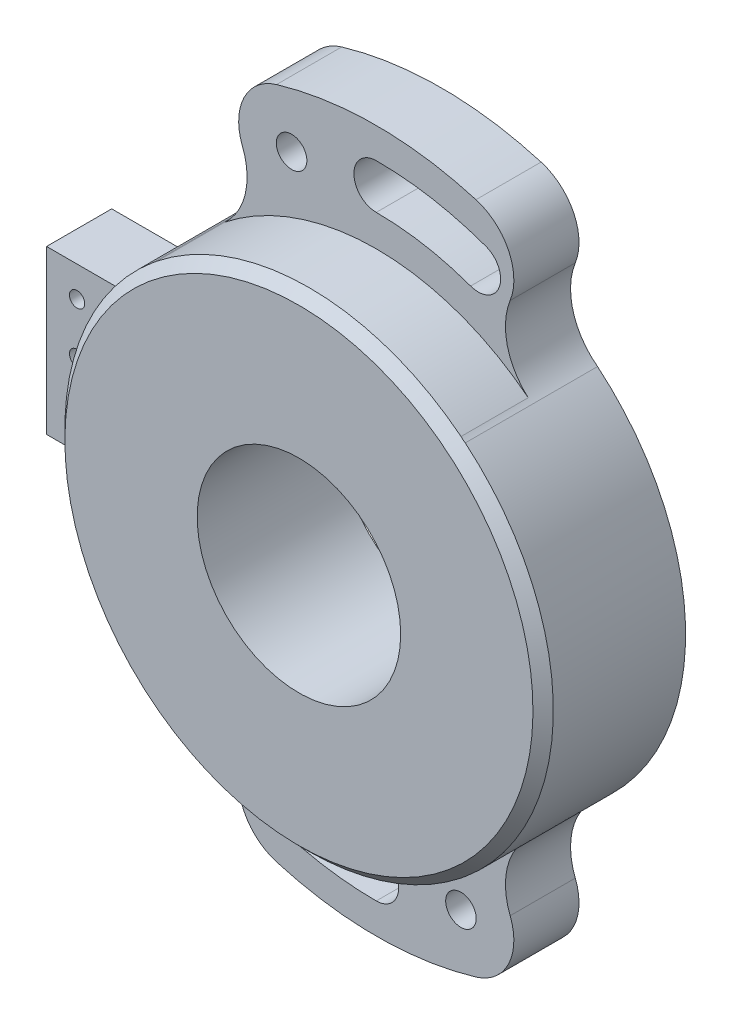
SolidWorks part; units mm, degrees
note: The reader was unsure of these and kept them because the rebuilt part matched: shared geometry of "Sketch1<3>".
material "PET"
ref_plane "Front Plane" through (0, 0, 0) normal (0, 0, 1) x (1, 0, 0)
ref_plane "Top Plane" through (0, 0, 0) normal (0, 1, 0) x (1, 0, 0)
ref_plane "Right Plane" through (0, 0, 0) normal (1, 0, 0) x (0, 0, -1)
sketch "Sketch1" plane through (0, 0, 0) normal (0, 0, 1) x (1, 0, 0)
  line L0 (5.8998, 16.2097) -> (-5.8998, -16.2097) construction
  line L1 (2.4007, 17.0821) -> (-2.4007, -17.0821) construction
  line L2 (-4.8993, 16.5396) -> (4.8993, -16.5396) construction
  line L3 (0, 17.25) -> (0, -17.25) construction
  line L4 (-17.25, 0) -> (17.25, 0) construction
  line L5 (0, -17.25) -> (0, 17.25) construction
  line L6 (-16.2, 4) -> (-16.2, -4)
  line L7 (-16.2, 4) -> (-11.3137, 4)
  line L8 (-16.2, -4) -> (-11.3137, -4)
  line L9 (-14.7, 4) -> (-14.7, -4) construction
  circle A0 centre (0, 0) radius 17.25 construction
  circle A1 centre (0, 0) radius 14.65 construction
  circle A2 centre (0, 0) radius 12
  circle A3 centre (-4.1608, 14.0467) radius 0.75
  arc A4 (0, 15.75) -> (5.3868, 14.8002) centre (0, 0) cw
  arc A5 (0, 13.55) -> (4.6344, 12.7328) centre (0, 0) cw
  arc A6 (5.3868, 14.8002) -> (4.6344, 12.7328) centre (5.0106, 13.7665) cw
  arc A7 (0, 13.55) -> (0, 15.75) centre (0, 14.65) cw
  arc A8 (-4.8993, 16.5396) -> (5.8998, 16.2097) centre (0, 0) cw
  arc A9 (-6.5784, 13.09) -> (-4.8993, 16.5396) centre (-4.1608, 14.0467) cw
  arc A10 (-6.5784, 13.09) -> (-7.6724, 9.2268) centre (-9.6516, 11.8738) cw
  arc A11 (6.5784, 13.09) -> (4.8993, 16.5396) centre (4.1608, 14.0467) ccw
  arc A12 (6.5784, 13.09) -> (7.6724, 9.2268) centre (9.6516, 11.8738) ccw
  circle A13 centre (4.1608, -14.0467) radius 0.75
  arc A14 (0, -13.55) -> (0, -15.75) centre (0, -14.65) cw
  arc A15 (0, -13.55) -> (-4.6344, -12.7328) centre (0, 0) cw
  arc A16 (-5.3868, -14.8002) -> (-4.6344, -12.7328) centre (-5.0106, -13.7665) cw
  arc A17 (0, -15.75) -> (-5.3868, -14.8002) centre (0, 0) cw
  arc A18 (6.5784, -13.09) -> (4.8993, -16.5396) centre (4.1608, -14.0467) cw
  arc A19 (6.5784, -13.09) -> (7.6724, -9.2268) centre (9.6516, -11.8738) cw
  arc A20 (4.8993, -16.5396) -> (-5.8998, -16.2097) centre (0, 0) cw
  arc A21 (-6.5784, -13.09) -> (-4.8993, -16.5396) centre (-4.1608, -14.0467) ccw
  arc A22 (-6.5784, -13.09) -> (-7.6724, -9.2268) centre (-9.6516, -11.8738) ccw
  circle A23 centre (-14.7, 2.5) radius 0.375
  circle A24 centre (-14.7, 0) radius 0.375
  circle A25 centre (-14.7, -2.5) radius 0.375
  circle A26 centre (0, 0) radius 5
  point P13 (0, 0)
  point P33 (-16.2, 0)
  point P56 (0, 0)
  dimension "D1" = 34.5
  dimension "D2" = 29.3
  dimension "D3" = 24
  dimension "D7" = 1.5
  dimension "D8" = 1.1
  dimension "D12" = 0.75
  dimension "D16" = 10
  dimension "D4" = 16.5
  dimension "D5" = 20
  dimension "D6" = 8
  dimension "D10" = 16.2
  dimension "D11" = 8
  dimension "D13" = 2.5
  dimension "D14" = 2.5
  dimension "D15" = 1.5
  dimension "D9" = 2
extrude "Boss-Extrude1" add sketch "Sketch1" along normal blind 7 contours A22 A2 A19 A12 A10 A26
extrude "Boss-Extrude2" add sketch "Sketch1<3>" along normal blind 3.2 contours A12 A11 A8 A9 A10 A2 A3 A5 A7 A4 A6 | A2 L7 L6 L8 A25 A24 A23 | A22 A21 A20 A18 A19 A2 A13 A14 A17 A16 A15
sketch "Sketch1<3>" plane through (0, 0, 0) normal (0, 0, 1) x (1, 0, 0) same geometry as "Sketch1"
chamfer "Chamfer1" distance 0.5 angle 45 1 edges at (-12, 0, 7)
